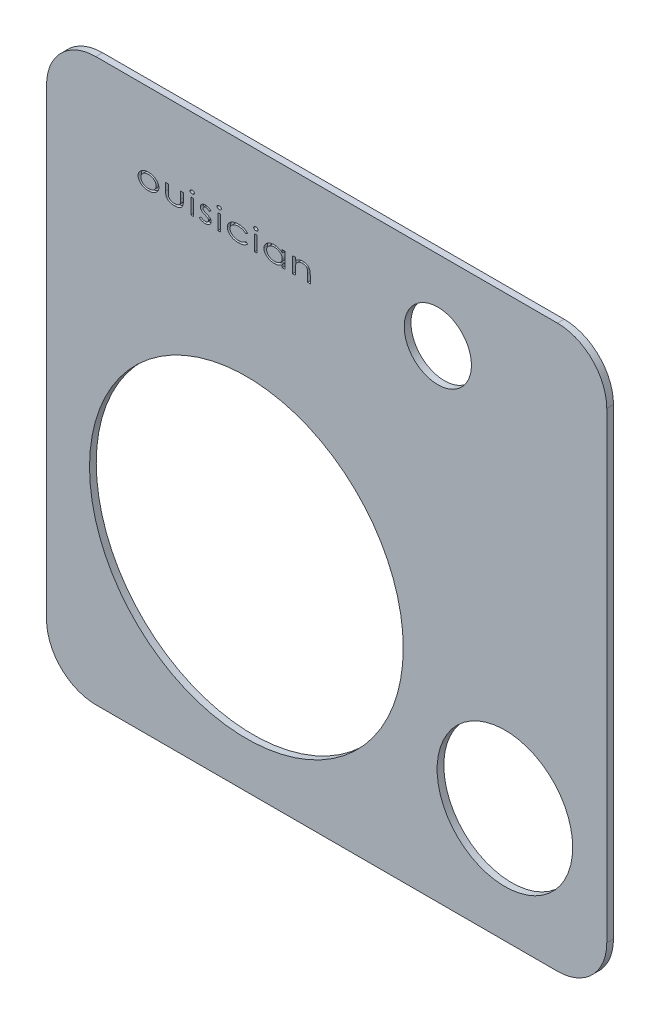
SolidWorks part; units mm, degrees
material "Pine"
ref_plane "Front Plane" through (0, 0, 0) normal (0, 0, 1) x (1, 0, 0)
ref_plane "Top Plane" through (0, 0, 0) normal (0, 1, 0) x (1, 0, 0)
ref_plane "Right Plane" through (0, 0, 0) normal (1, 0, 0) x (0, 0, -1)
sketch "Sketch1" plane through (0, 0, 0) normal (0, 0, 1) x (1, 0, 0)
  line L1 (0, 0) -> (500, 0)
  line L2 (0, 0) -> (0, 501)
  line L3 (0, 501) -> (500, 501)
  line L4 (500, 0) -> (500, 501)
  dimension "D1" = 500
  dimension "D2" = 501
extrude "Boss-Extrude1" add sketch "Sketch1" along normal blind 6
fillet "Fillet1" radius 44 4 edges at (0, 0, 3) (500, 0, 3) (0, 501, 3) (500, 501, 3)
sketch "Sketch2" plane through (0, 0, 6) normal (0, 0, 1) x (1, 0, 0)
  circle A0 centre (178.369, 181.0347) radius 156
  dimension "D1" = 312
sketch "Sketch3" plane through (0, 0, 6) normal (0, 0, 1) x (1, 0, 0)
  circle A1 centre (178.369, 181.0347) radius 140
  dimension "D1" = 280
extrude "Cut-Extrude2" cut sketch "Sketch3" against normal through all
sketch "Sketch4" plane through (0, 0, 6) normal (0, 0, 1) x (1, 0, 0)
  circle A0 centre (409.1034, 102.5162) radius 72.5
  dimension "D1" = 145
sketch "Sketch5" plane through (0, 0, 6) normal (0, 0, 1) x (1, 0, 0)
  circle A0 centre (409.1034, 102.5162) radius 60.5
  dimension "D1" = 121
extrude "Cut-Extrude3" cut sketch "Sketch5" against normal through all
sketch "Sketch6" plane through (0, 0, 6) normal (0, 0, 1) x (1, 0, 0)
  line L0 (500, 360) -> (0, 360)
  line L1 (500, 44) -> (500, 457) construction
  line L2 (0, 457) -> (0, 44) construction
  line L3 (44, 0) -> (456, 0) construction
  line L4 (456, 501) -> (44, 501) construction
  circle A0 centre (349.2286, 430) radius 50
  circle A1 centre (349.2286, 430) radius 30
  dimension "D1" = 100
  dimension "D3" = 60
  dimension "D2" = 360
  dimension "D4" = 71
extrude "Cut-Extrude5" cut sketch "Sketch6" against normal through all contours A1 region at (349.2286, 430, 6)
sketch "Sketch7" plane through (0, 0, 6) normal (0, 0, 1) x (1, 0, 0)
  line L0 (0, 457) -> (0, 44) construction
  line L1 (456, 501) -> (44, 501) construction
  text T0 "ouisician" font "Century Gothic" height in points 72
  dimension "D1" = 80
  dimension "D2" = 80
extrude "Cut-Extrude6" cut sketch "Sketch7" against normal blind 3
sketch "Sketch10" plane through (0, 0, 6) normal (0, 0, 1) x (1, 0, 0)
  line L0 (0, 366) -> (500, 366)
  line L1 (0, 457) -> (0, 44) construction
  line L2 (500, 44) -> (500, 457) construction
  line L3 (456, 501) -> (44, 501) construction
  line L4 (0, 360) -> (500, 360)
  line L5 (44, 0) -> (456, 0) construction
  dimension "D1" = 500
  dimension "D2" = 135
  dimension "D3" = 360
